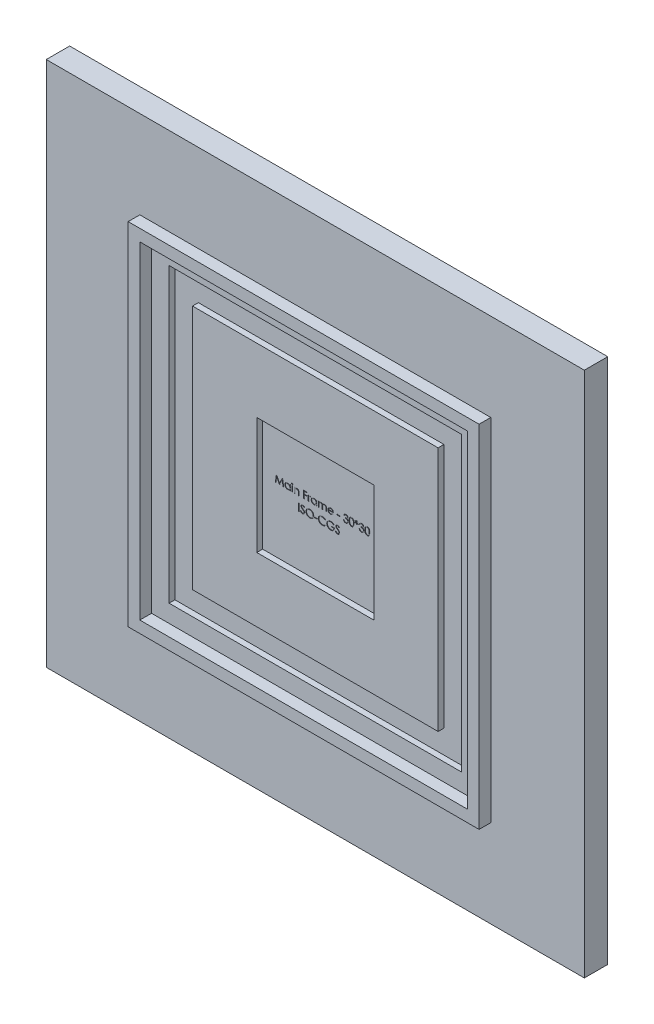
SolidWorks part; units mm, degrees
ref_plane "정면" through (0, 0, 0) normal (0, 0, 1) x (1, 0, 0)
ref_plane "윗면" through (0, 0, 0) normal (0, 1, 0) x (1, 0, 0)
ref_plane "우측면" through (0, 0, 0) normal (1, 0, 0) x (0, 0, -1)
sketch "스케치2" plane through (0, 0, 0) normal (0, 0, 1) x (1, 0, 0)
  line L1 (-230, 225) -> (230, 225)
  line L2 (-230, 225) -> (-230, -225)
  line L3 (-230, -225) -> (230, -225)
  line L4 (230, 225) -> (230, -225)
  line L5 (-230, 225) -> (230, -225) construction
  line L6 (-230, -225) -> (230, 225) construction
  point P0 (0, 0)
  dimension "D1" = 460
  dimension "D2" = 450
extrude "보스-돌출1" add sketch "스케치2" along normal blind 20
sketch "스케치3" plane through (0, 0, 20) normal (0, 0, 1) x (1, 0, 0)
  line L1 (-140, 140) -> (140, 140)
  line L2 (-140, 140) -> (-140, -140)
  line L3 (-140, -140) -> (140, -140)
  line L4 (140, 140) -> (140, -140)
  line L5 (-140, 140) -> (140, -140) construction
  line L6 (-140, -140) -> (140, 140) construction
  line L7 (-150, 150) -> (150, 150)
  line L8 (-150, 150) -> (-150, -150)
  line L9 (-150, -150) -> (150, -150)
  line L10 (150, 150) -> (150, -150)
  line L11 (-150, 150) -> (150, -150) construction
  line L12 (-150, -150) -> (150, 150) construction
  point P0 (0, 0)
  point P6 (0, 0)
  dimension "D1" = 280
  dimension "D2" = 280
extrude "보스-돌출2" add sketch "스케치3" along normal blind 10
sketch "스케치6" plane through (0, 0, 20) normal (0, 0, 1) x (1, 0, 0)
  line L1 (-50, 50) -> (50, 50)
  line L2 (-50, 50) -> (-50, -50)
  line L3 (-50, -50) -> (50, -50)
  line L4 (50, 50) -> (50, -50)
  line L5 (-50, 50) -> (50, -50) construction
  line L6 (-50, -50) -> (50, 50) construction
  line L7 (-105, 105) -> (105, 105)
  line L8 (-105, 105) -> (-105, -105)
  line L9 (-105, -105) -> (105, -105)
  line L10 (105, 105) -> (105, -105)
  line L11 (-105, 105) -> (105, -105) construction
  line L12 (-105, -105) -> (105, 105) construction
  line L13 (-125, 125) -> (125, 125)
  line L14 (-125, 125) -> (-125, -125)
  line L15 (-125, -125) -> (125, -125)
  line L16 (125, 125) -> (125, -125)
  line L17 (-125, 125) -> (125, -125) construction
  line L18 (-125, -125) -> (125, 125) construction
  point P0 (0, 0)
  point P6 (0, 0)
  point P11 (0, 0)
  dimension "D1" = 100
  dimension "D2" = 250
  dimension "10" = 100
  dimension "D3" = 250
  dimension "D4" = 20
  dimension "D5" = 20
extrude "컷-돌출2" cut sketch "스케치6" against normal blind 5 contours L16 L13 L14 L15 L7 L10 L9 L8 | L4 L1 L2 L3 region at (0, 0, 20) region at (0, 121.4645, 20)
sketch "스케치7" plane through (0, 0, 15) normal (0, 0, 1) x (1, 0, 0)
  text T0 "Main Frame - 30*30\r\n        ISO-CGS" font "Century Gothic" height in points 24
extrude "컷-돌출3" cut sketch "스케치7" against normal blind 0.4
